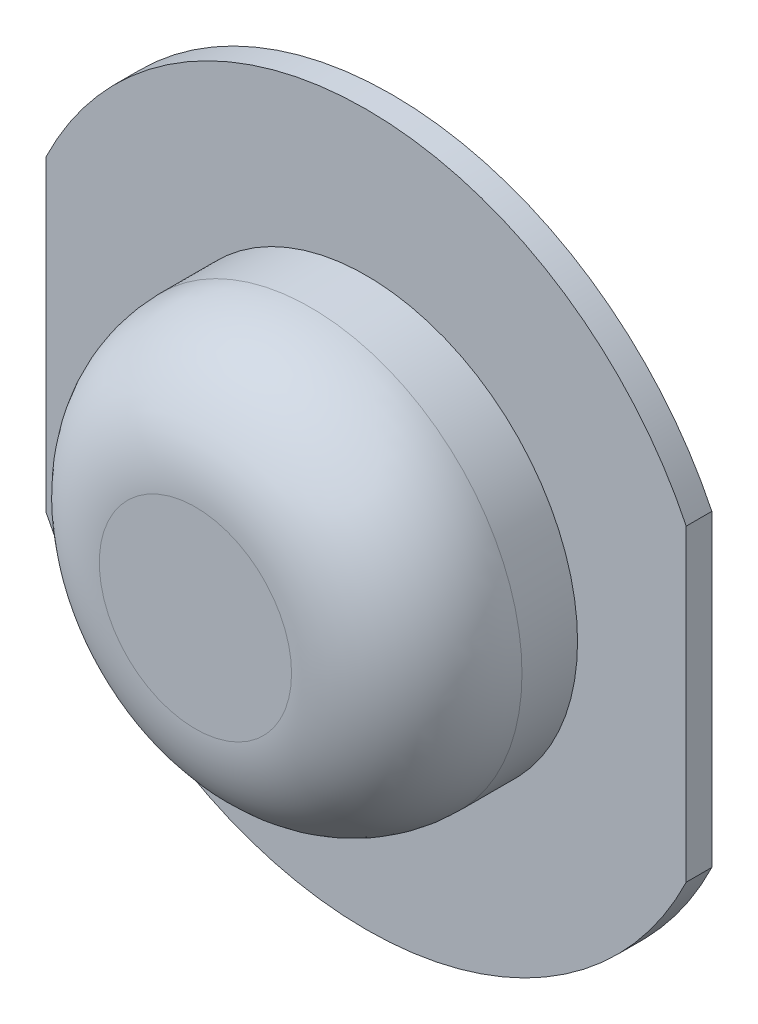
SolidWorks part; units mm, degrees
material "Silicon"
ref_plane "Front Plane" through (0, 0, 0) normal (0, 0, 1) x (1, 0, 0)
ref_plane "Top Plane" through (0, 0, 0) normal (0, 1, 0) x (1, 0, 0)
ref_plane "Right Plane" through (0, 0, 0) normal (1, 0, 0) x (0, 0, -1)
ref_axis "Axis1" through (0, 0, 0) along (0, 0, 1)
sketch "Sketch1" plane through (0, 0, 0) normal (0, 0, 1) x (1, 0, 0)
  line L0 (50, 24.0884) -> (50, -24.0884)
  line L1 (-50, 24.0884) -> (-50, -24.0884)
  arc A0 (-50, -24.0884) -> (50, -24.0884) centre (0, 0) ccw
  arc A1 (50, 24.0884) -> (-50, 24.0884) centre (0, 0) ccw
  dimension "D1" = 55.5
  dimension "D2" = 100
extrude "Boss-Extrude1" add sketch "Sketch1" along normal blind 4
sketch "Sketch5" plane through (0, 0, 0) normal (0, 0, 1) x (1, 0, 0)
  line L0 (0, 0) -> (0, -41.75) construction
  line L1 (43.25, 43.25) -> (-43.25, 43.25) construction
  line L2 (43.25, 43.25) -> (43.25, -43.25) construction
  line L3 (43.25, -43.25) -> (-43.25, -43.25) construction
  line L4 (-43.25, 43.25) -> (-43.25, -43.25) construction
  line L5 (43.25, 43.25) -> (-43.25, -43.25) construction
  line L6 (43.25, -43.25) -> (-43.25, 43.25) construction
  line L7 (0, 0) -> (0, 41.75) construction
  line L8 (0, 0) -> (-41.75, 0) construction
  line L9 (0, 0) -> (41.75, 0) construction
  line L11 (-36, 36) -> (36, 36) construction
  line L12 (-36, 36) -> (-36, -36) construction
  line L13 (-36, -36) -> (36, -36) construction
  line L14 (36, 36) -> (36, -36) construction
  line L15 (-36, 36) -> (36, -36) construction
  line L16 (-36, -36) -> (36, 36) construction
  circle A0 centre (18.497, -18.497) radius 24.753 construction
  circle A1 centre (-18.497, -18.497) radius 24.753 construction
  circle A2 centre (18.497, 18.497) radius 24.753 construction
  circle A3 centre (-18.497, 18.497) radius 24.753 construction
  spline S0 degree 3 poles (45.3558, 18.4579) (39.9657, 0) (45.3558, -18.4579) (38.0677, -38.0677) (18.4579, -45.3558) (0, -39.9657) (-18.4579, -45.3558) (-38.0677, -38.0677) (-45.3558, -18.4579) (-39.9657, 0) (-45.3558, 18.4579) (-38.0677, 38.0677) (-18.4579, 45.3558) (0, 39.9657) (18.4579, 45.3558) (38.0677, 38.0677) (45.3558, 18.4579) (39.9657, 0) (45.3558, -18.4579) knots -0.188146 -0.125 -0.061854 0 0.061854 0.125 0.188146 0.25 0.311854 0.375 0.438146 0.5 0.561854 0.625 0.688146 0.75 0.811854 0.875 0.938146 1 1.061854 1.125 1.188146 only from (41.75, 0) to (41.75, 0)
  point P0 (0, 0)
  dimension "D1" = 86.5
  dimension "D2" = 83.5
  dimension "D3" = 72
extrude "Boss-Extrude2" [suppressed] add sketch "Sketch5" along normal blind 29.78 draft 4
fillet "Fillet1" [suppressed] radius 12
sketch "Sketch6" plane through (0, 0, 0) normal (0, 0, -1) x (-1, 0, 0)
  line L1 (-26.27, -26.27) -> (26.27, -26.27)
  line L2 (-26.27, -26.27) -> (-26.27, 26.27)
  line L3 (-26.27, 26.27) -> (26.27, 26.27)
  line L4 (26.27, -26.27) -> (26.27, 26.27)
  line L5 (-26.27, -26.27) -> (26.27, 26.27) construction
  line L6 (-26.27, 26.27) -> (26.27, -26.27) construction
  point P0 (0, 0)
  dimension "D1" = 52.54
extrude "Cut-Extrude2" cut sketch "Sketch6" against normal blind 0.25
sketch "Sketch7" plane through (0, 0, 0) normal (0, 1, 0) x (1, 0, 0)
  line L0 (0, -0.25) -> (0, -25.25)
  line L1 (26.27, -0.25) -> (-26.27, -0.25) construction
  line L2 (0, -0.25) -> (25, -0.25)
  arc A0 (0, -25.25) -> (25, -0.25) centre (0, -0.25) ccw
  dimension "D1" = 25
revolve "Cut-Revolve1" cut sketch "Sketch7" angle 360 about L0
sketch "Sketch8" plane through (0, 0, 0.25) normal (0, 0, -1) x (-1, 0, 0)
  line L0 (19.5512, 19.5512) -> (-19.5512, -19.5512) construction
  line L1 (-26.27, 26.27) -> (-26.27, -26.27) construction
  line L3 (-19.887, -15.1494) -> (-15.1494, -19.887)
  line L4 (-19.887, -15.1494) -> (-22.5387, -17.8011)
  line L5 (-22.5387, -20.6295) -> (-20.6295, -22.5387)
  line L6 (-15.1494, -19.887) -> (-17.8011, -22.5387)
  line L7 (-19.887, -15.1494) -> (-19.2153, -23.9529) construction
  line L8 (-23.9529, -19.2153) -> (-15.1494, -19.887) construction
  circle A0 centre (0, 0) radius 25 construction
  arc A1 (-22.5387, -17.8011) -> (-22.5387, -20.6295) centre (-21.1245, -19.2153) ccw
  arc A2 (-20.6295, -22.5387) -> (-17.8011, -22.5387) centre (-19.2153, -21.1245) ccw
  point P4 (0, 0)
  point P45 (0, 0)
  dimension "D4" = 2
  dimension "D1" = 45
  dimension "D2" = 5.75
  dimension "D3" = 6.7
extrude "Cut-Extrude3" cut sketch "Sketch8" against normal blind 0.3
pattern_circular "CirPattern1" count 4 over 360 about axis through (0, 0, 0) along (0, 0, 1) of "Cut-Extrude3"
sketch "Sketch9" plane through (0, 0, 4) normal (0, 0, 1) x (1, 0, 0)
  circle A0 centre (0, 0) radius 33.02
  dimension "D1" = 66.04
extrude "Boss-Extrude3" add sketch "Sketch9" along normal blind 26.68 and the other way blind 3
fillet "Fillet2" radius 18 1 edges at (33.02, 0, 30.68)
sketch "Sketch10" plane through (0, 0, 0) normal (0, 0, -1) x (-1, 0, 0)
  line L0 (50, -24.0884) -> (-50, 24.0884) construction
  point P4 (0, 0)
